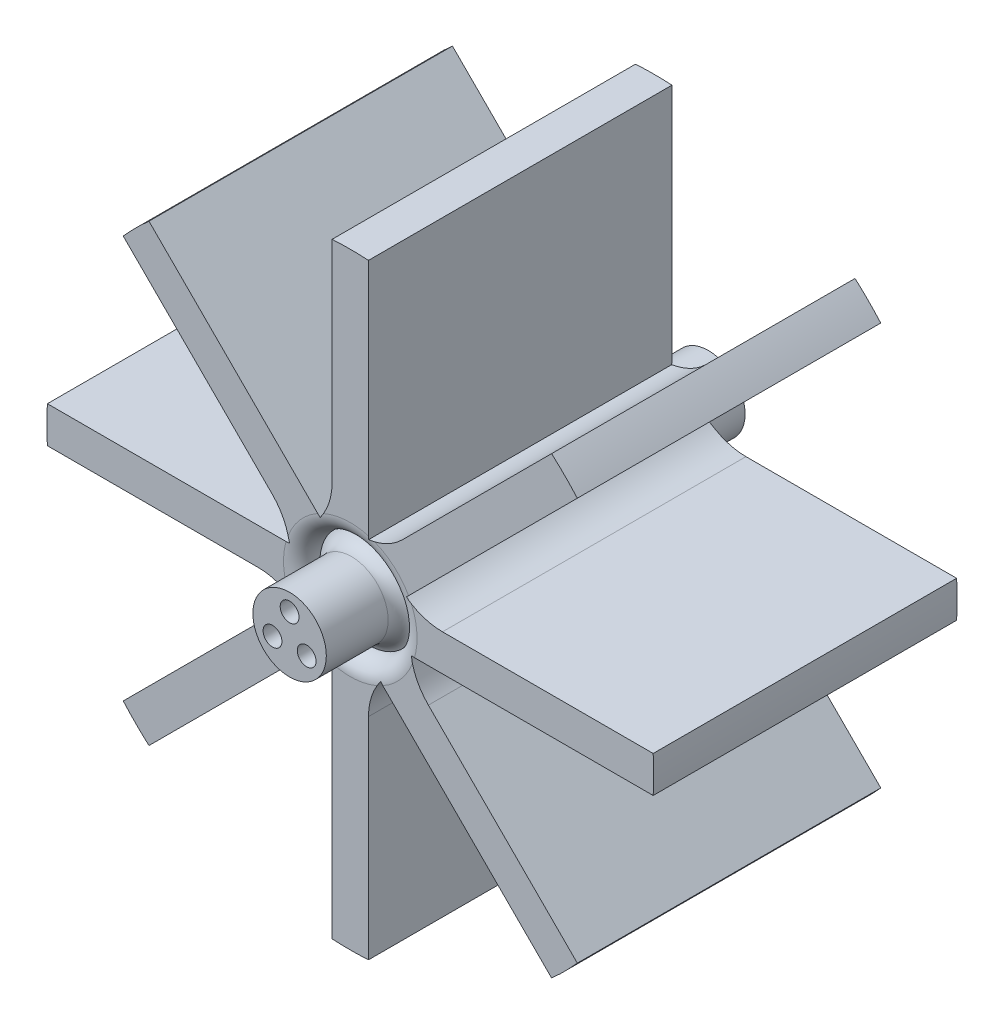
SolidWorks part; units mm, degrees
ref_plane "Front Plane" through (0, 0, 0) normal (0, 0, 1) x (1, 0, 0)
ref_plane "Top Plane" through (0, 0, 0) normal (0, 1, 0) x (1, 0, 0)
ref_plane "Right Plane" through (0, 0, 0) normal (1, 0, 0) x (0, 0, -1)
sketch "Sketch1" plane through (0, 0, 0) normal (0, 0, 1) x (1, 0, 0)
  line L2 (-3, 50) -> (-3, 7.2426)
  line L8 (-50, -3) -> (-7.2426, -3)
  line L12 (3, 50) -> (3, 7.2426)
  line L14 (-50, 3) -> (-7.2426, 3)
  line L16 (7.2426, -3) -> (37.4767, -33.234)
  line L32 (3, -7.2426) -> (33.234, -37.4767)
  line L34 (-3, -7.2426) -> (-3, -50)
  line L35 (-7.2426, 3) -> (-37.4767, 33.234)
  line L37 (-7.2426, -3) -> (-37.4767, -33.234)
  line L38 (7.2426, 3) -> (50, 3)
  line L39 (3, 7.2426) -> (33.234, 37.4767)
  line L41 (-3, 7.2426) -> (-33.234, 37.4767)
  line L48 (7.2426, 3) -> (37.4767, 33.234)
  line L50 (3, -7.2426) -> (3, -50)
  line L52 (7.2426, -3) -> (50, -3)
  line L53 (-3, -7.2426) -> (-33.234, -37.4767)
  circle A0 centre (0, 0) radius 50
  dimension "D1" = 100
extrude "Boss-Extrude1" add sketch "Sketch1" along normal blind 50 contours L48 A0 L39 L12 L2 L41 L35 L14 L8 L37 L53 L34 L50 L32 L16 L52 L38 region at (0, 0, 0)
sketch "Sketch2" plane through (0, 0, 50) normal (0, 0, 1) x (1, 0, 0)
  circle A0 centre (0, 0) radius 10
  dimension "D1" = 20
extrude "Boss-Extrude3" add sketch "Sketch2" along normal blind 6
extrude "Boss-Extrude4" add sketch "Sketch2<2>" against normal blind 50
sketch "Sketch2<2>" plane through (0, 0, 50) normal (0, 0, 1) x (1, 0, 0) same geometry as "Sketch2"
sketch "Sketch3" plane through (0, 0, 0) normal (0, 0, -1) x (-1, 0, 0)
  circle A0 centre (0, 0) radius 6.05
  dimension "D1" = 12.1
extrude "Boss-Extrude5" add sketch "Sketch3" along normal blind 9
sketch "Sketch4" plane through (0, 0, 0) normal (0, 0, -1) x (-1, 0, 0)
  circle A0 centre (0, 0) radius 8.05
  circle A1 centre (0, 0) radius 6.05 construction
  circle A2 centre (0, 0) radius 6.05
  dimension "D1" = 2
extrude "Cut-Extrude2" cut sketch "Sketch4" against normal blind 3
fillet "Fillet1" radius 3 2 edges at (-8.05, 0, 0) (-6.05, 0, 3)
fillet "Fillet2" radius 10 8 edges at (4.624, 8.8667, 25.0949) (9.5394, 3, 25.0949) (8.8667, -4.624, 25.0949) (3, -9.5394, 25.0949) (-4.624, -8.8667, 25.0949) (-9.5394, -3, 25.0949) (-8.8667, 4.624, 25.0949) (-3, 9.5394, 25.0949)
sketch "Sketch8" plane through (0, 0, 56) normal (0, 0, 1) x (1, 0, 0)
  circle A0 centre (0, 0) radius 10
extrude "Cut-Extrude6" cut sketch "Sketch8" against normal blind 6
sketch "Sketch9" plane through (0, 0, 50) normal (0, 0, 1) x (1, 0, 0)
  circle A0 centre (0, 0) radius 6.05
  dimension "D1" = 12.1
extrude "Boss-Extrude6" add sketch "Sketch9" along normal blind 10
sketch "Sketch10" plane through (0, 0, 50) normal (0, 0, 1) x (1, 0, 0)
  circle A0 centre (0, 0) radius 8
  dimension "D1" = 16
extrude "Cut-Extrude7" cut sketch "Sketch10" against normal blind 3
fillet "Fillet3" radius 3 1 edges at (8, 0, 50)
sketch "Sketch11" plane through (0, 0, 60) normal (0, 0, 1) x (1, 0, 0)
  circle A0 centre (0, 0) radius 6.05
extrude "Boss-Extrude7" add sketch "Sketch11" against normal blind 23
fillet "Fillet4" radius 3 1 edges at (6.05, 0, 47)
sketch "Sketch12" plane through (0, 0, 60) normal (0, 0, 1) x (1, 0, 0)
  line L0 (0, 3.2505) -> (-2.815, -1.6252)
  line L1 (0, 3.2505) -> (2.815, -1.6252)
  line L2 (2.815, -1.6252) -> (-2.815, -1.6252)
  line L3 (0, 3.2505) -> (0, 0)
  line L4 (0, 0) -> (-2.815, -1.6252)
  line L5 (0, 0) -> (2.815, -1.6252)
  line L7 (0, 5.3893) -> (-1.8522, 4.3199)
  line L8 (-1.8522, 4.3199) -> (-1.8522, 2.1811)
  line L9 (-1.8522, 2.1811) -> (0, 1.1117)
  line L10 (0, 1.1117) -> (1.8522, 2.1811)
  line L11 (1.8522, 2.1811) -> (1.8522, 4.3199)
  line L12 (1.8522, 4.3199) -> (0, 5.3893)
  line L13 (2.815, 0.5135) -> (0.9628, -0.5558)
  line L14 (0.9628, -0.5558) -> (0.9628, -2.6946)
  line L15 (0.9628, -2.6946) -> (2.815, -3.764)
  line L16 (2.815, -3.764) -> (4.6672, -2.6946)
  line L17 (4.6672, -2.6946) -> (4.6672, -0.5558)
  line L18 (4.6672, -0.5558) -> (2.815, 0.5135)
  line L19 (-2.8438, 0.5134) -> (-4.6815, -0.5809)
  line L20 (-4.6815, -0.5809) -> (-4.6527, -2.7195)
  line L21 (-4.6527, -2.7195) -> (-2.7862, -3.7638)
  line L22 (-2.7862, -3.7638) -> (-0.9485, -2.6696)
  line L23 (-0.9485, -2.6696) -> (-0.9773, -0.531)
  line L24 (-0.9773, -0.531) -> (-2.8438, 0.5134)
  circle A0 centre (0, 3.2505) radius 1.55
  circle A1 centre (2.815, -1.6252) radius 1.55
  circle A2 centre (-2.815, -1.6252) radius 1.55
  circle A3 centre (0, 3.2505) radius 1.8522 construction
  circle A4 centre (2.815, -1.6252) radius 1.8522 construction
  circle A5 centre (-2.815, -1.6252) radius 1.8522 construction
  dimension "D2" = 3.1
  dimension "D1" = 5.63
extrude "Cut-Extrude8" cut sketch "Sketch12" against normal blind 6 contours L1 A0 L0 | L3 A0 L1 | L0 A0 L3 | L0 A2 L2 | L4 A2 L0 | L2 A2 L4 | L2 A1 L1 | L1 A1 L5 | L5 A1 L2 region at (-0.2644, 2.2637, 60) region at (0, 3.4478, 60) region at (0.2644, 2.2637, 60) region at (-2.0926, -0.9029, 60) region at (-2.9859, -1.7239, 60) region at (2.9859, -1.7239, 60) region at (2.0926, -0.9029, 60) region at (-1.8282, -1.3608, 60) region at (1.8282, -1.3608, 60)
extrude "Cut-Extrude9" cut sketch "Sketch12<3>" against normal blind 3 from offset 3 contours A1 L5 L14 L2 | A1 L1 L13 L5 | A1 L2 L14 L15 L16 L17 L18 L13 L1 | A2 L0 L24 L19 L20 L21 L22 L23 L2 | A2 L4 L23 L24 L0 | A2 L2 L23 L4 | A0 L1 L10 L11 L12 L7 L8 L9 L0 | A0 L0 L9 L3 | A0 L3 L10 L1 region at (-0.3858, 1.5489, 60) region at (-0.8962, 1.8036, 60) region at (0.3858, 1.5489, 60) region at (-1.5293, -0.4387, 60) region at (-2.0136, -0.1236, 60) region at (2.3802, 0.1972, 60) region at (1.5343, -0.4403, 60) region at (1.1485, -1.1086, 60) region at (-1.1523, -1.1127, 60) offset against normal yes
sketch "Sketch12<3>" plane through (0, 0, 60) normal (0, 0, 1) x (1, 0, 0) same geometry as "Sketch12"
equation "\"a\"=100"
equation "\"D1@Sketch1\"=\"a\""
equation "\"c\"=4.5"
equation "\"b\"=25"
